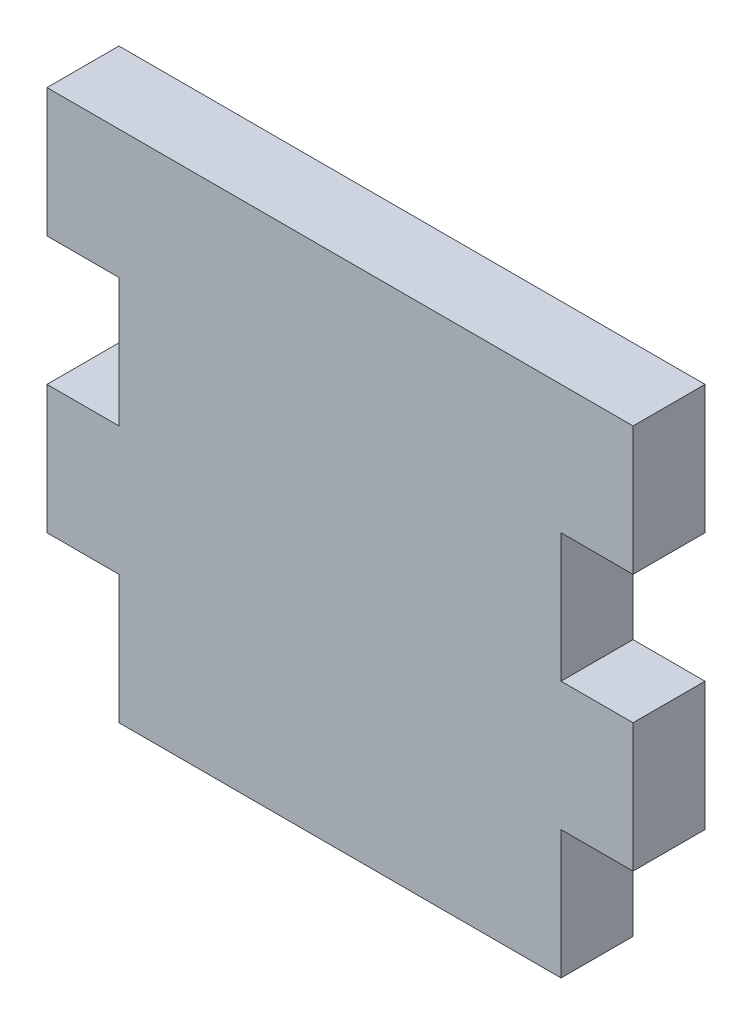
SolidWorks part; units mm, degrees
ref_plane "Front Plane" through (0, 0, 0) normal (0, 0, 1) x (1, 0, 0)
ref_plane "Top Plane" through (0, 0, 0) normal (0, 1, 0) x (1, 0, 0)
ref_plane "Right Plane" through (0, 0, 0) normal (1, 0, 0) x (0, 0, -1)
sketch "Sketch1" plane through (0, 0, 0) normal (0, 0, 1) x (1, 0, 0)
  line L1 (-88.0852, 14.1109) -> (-44.6512, 14.1109)
  line L2 (-88.0852, 14.1109) -> (-88.0852, -23.9891)
  line L3 (-88.0852, -23.9891) -> (-44.6512, -23.9891)
  line L4 (-44.6512, 14.1109) -> (-44.6512, -23.9891)
  dimension "D1" = 38.1
  dimension "D2" = 43.434
extrude "Boss-Extrude1" add sketch "Sketch1" along normal blind 5.334
sketch "Sketch2" plane through (0, 0, 5.334) normal (0, 0, 1) x (1, 0, 0)
  line L0 (-88.0852, 14.1109) -> (-88.0852, -23.9891) construction
  line L1 (-88.0852, -23.9891) -> (-82.7512, -23.9891)
  line L2 (-88.0852, -23.9891) -> (-88.0852, -14.4641)
  line L3 (-88.0852, -14.4641) -> (-82.7512, -14.4641)
  line L4 (-82.7512, -23.9891) -> (-82.7512, -14.4641)
  line L5 (-88.0852, -4.9391) -> (-82.7512, -4.9391)
  line L6 (-88.0852, -4.9391) -> (-88.0852, 4.5859)
  line L7 (-88.0852, 4.5859) -> (-82.7512, 4.5859)
  line L8 (-82.7512, -4.9391) -> (-82.7512, 4.5859)
  line L9 (-82.7512, 4.5859) -> (-82.7512, 14.1109) construction
  line L10 (-44.6512, 14.1109) -> (-88.0852, 14.1109) construction
  line L11 (-82.7512, -4.9391) -> (-82.7512, -14.4641) construction
  line L12 (-66.3682, 14.1109) -> (-66.3682, -23.9891) construction
  line L13 (-88.0852, -23.9891) -> (-44.6512, -23.9891) construction
  line L14 (-49.9852, -4.9391) -> (-49.9852, -14.4641) construction
  line L15 (-49.9852, 4.5859) -> (-49.9852, 14.1109) construction
  line L16 (-49.9852, -4.9391) -> (-49.9852, 4.5859)
  line L17 (-44.6512, 4.5859) -> (-49.9852, 4.5859)
  line L18 (-44.6512, -4.9391) -> (-44.6512, 4.5859)
  line L19 (-44.6512, -4.9391) -> (-49.9852, -4.9391)
  line L20 (-49.9852, -23.9891) -> (-49.9852, -14.4641)
  line L21 (-44.6512, -14.4641) -> (-49.9852, -14.4641)
  line L22 (-44.6512, -23.9891) -> (-44.6512, -14.4641)
  line L23 (-44.6512, -23.9891) -> (-49.9852, -23.9891)
  dimension "D1" = 5.334
extrude "Cut-Extrude1" cut sketch "Sketch2" against normal through all
equation "\"MDF\"= .21in"
equation "\"Foamcore\"= .13in"
equation "\"Gmaterial\"= \"MDF\""
equation "\"D1@Boss-Extrude1\"=\"MDF\""
equation "\"D1@Sketch2\"=\"MDF\""
equation "\"D2@Sketch1\"=\"MDF\"+\"MDF\"+1.29"
